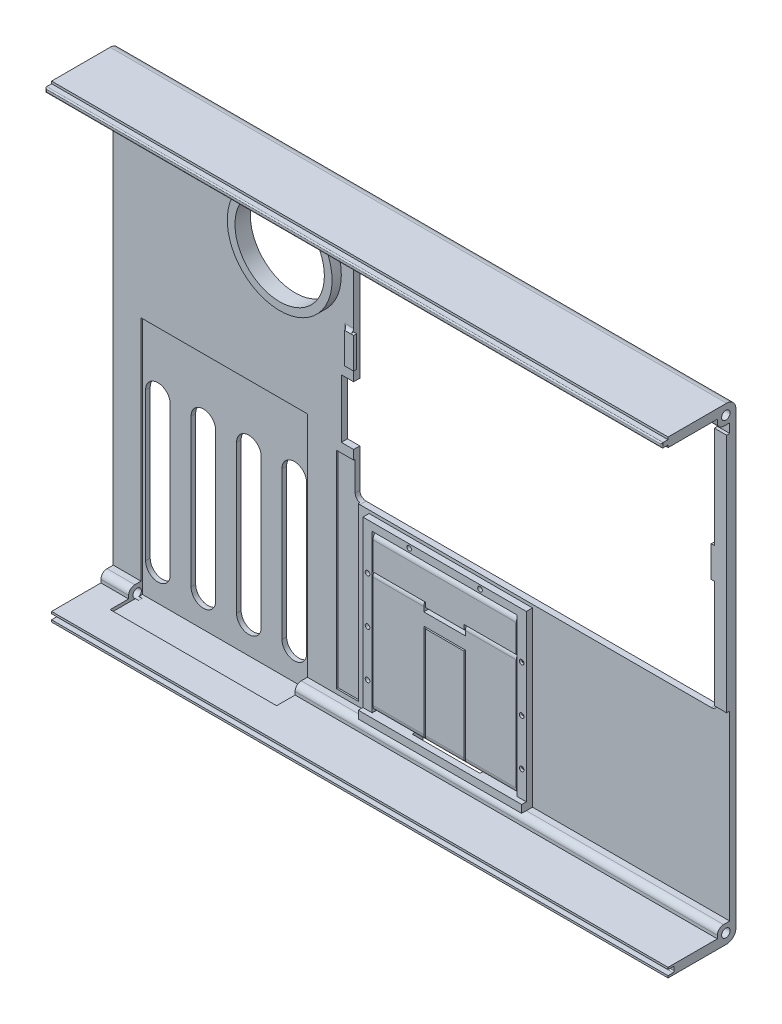
SolidWorks part; units mm, degrees
ref_plane "Front Plane" through (0, 0, 0) normal (0, 0, 1) x (1, 0, 0)
ref_plane "Top Plane" through (0, 0, 0) normal (0, 1, 0) x (1, 0, 0)
ref_plane "Right Plane" through (0, 0, 0) normal (1, 0, 0) x (0, 0, -1)
sketch "Sketch1" plane through (0, 0, 0) normal (0, 0, 1) x (1, 0, 0)
  line L1 (105, -90.3987) -> (-95, -90.3987)
  line L2 (105, -90.3987) -> (105, 61.6013)
  line L3 (105, 61.6013) -> (-95, 61.6013)
  line L4 (-95, -90.3987) -> (-95, 61.6013)
  line L5 (105, -90.3987) -> (-95, 61.6013) construction
  line L6 (105, 61.6013) -> (-95, -90.3987) construction
  point P0 (5, -14.3987)
  dimension "D1" = 200
  dimension "D2" = 152
extrude "body" add sketch "Sketch1" along normal blind 2
sketch "Sketch3" plane through (0, 0, 0) normal (0, 0, -1) x (-1, 0, 0)
  line L0 (95, -54.3987) -> (-105, -54.3987) construction
  line L1 (95, 61.6013) -> (95, -90.3987) construction
  line L2 (-105, -90.3987) -> (-105, 61.6013) construction
  line L3 (66.25, -78.3987) -> (66.25, -30.3987) construction
  line L4 (62.25, -78.3987) -> (62.25, -30.3987)
  line L5 (70.25, -78.3987) -> (70.25, -30.3987)
  line L6 (95, -30.3987) -> (-105, -30.3987) construction
  line L7 (81, -78.3987) -> (81, -30.3987) construction
  line L8 (95, -78.3987) -> (-105, -78.3987) construction
  line L9 (77, -78.3987) -> (77, -30.3987)
  line L10 (85, -78.3987) -> (85, -30.3987)
  line L11 (51.5, -78.3987) -> (51.5, -30.3987) construction
  line L12 (47.5, -78.3987) -> (47.5, -30.3987)
  line L13 (55.5, -78.3987) -> (55.5, -30.3987)
  line L14 (36.75, -78.3987) -> (36.75, -30.3987) construction
  line L15 (32.75, -78.3987) -> (32.75, -30.3987)
  line L16 (40.75, -78.3987) -> (40.75, -30.3987)
  line L17 (95, -90.3987) -> (95, 61.6013) construction
  line L18 (-105, 61.6013) -> (95, 61.6013) construction
  line L19 (95, -90.3987) -> (-105, -90.3987) construction
  line L20 (-105, -90.3987) -> (-105, 61.6013) construction
  circle A0 centre (38, 34.1013) radius 14.5
  arc A1 (62.25, -78.3987) -> (70.25, -78.3987) centre (66.25, -78.3987) ccw
  arc A2 (70.25, -30.3987) -> (62.25, -30.3987) centre (66.25, -30.3987) ccw
  arc A3 (77, -78.3987) -> (85, -78.3987) centre (81, -78.3987) ccw
  arc A4 (85, -30.3987) -> (77, -30.3987) centre (81, -30.3987) ccw
  arc A5 (47.5, -78.3987) -> (55.5, -78.3987) centre (51.5, -78.3987) ccw
  arc A6 (55.5, -30.3987) -> (47.5, -30.3987) centre (51.5, -30.3987) ccw
  arc A7 (32.75, -78.3987) -> (40.75, -78.3987) centre (36.75, -78.3987) ccw
  arc A8 (40.75, -30.3987) -> (32.75, -30.3987) centre (36.75, -30.3987) ccw
  point P10 (66.25, -54.3987)
  point P21 (81, -54.3987)
  point P27 (51.5, -54.3987)
  point P34 (36.75, -54.3987)
  dimension "D1" = 29
  dimension "D2" = 27.5
  dimension "D3" = 57
  dimension "D4" = 10
  dimension "D5" = 12
  dimension "D6" = 24
  dimension "D7" = 6.75
  dimension "D8" = 8
  dimension "D9" = 8
  dimension "D10" = 8
  dimension "D11" = 8
  dimension "D12" = 6.75
  dimension "D13" = 52.25
  dimension "D14" = 6.75
extrude "fan_exhaust_grill" cut sketch "Sketch3" against normal through all
sketch "Sketch12" plane through (0, 0, 2) normal (0, 0, 1) x (1, 0, 0)
  line L0 (-95, -90.3987) -> (-95, 61.6013) construction
  line L1 (105, -90.3987) -> (-95, -90.3987)
  line L2 (105, -90.3987) -> (105, -84.3987)
  line L3 (105, -84.3987) -> (-95, -84.3987)
  line L4 (-95, -90.3987) -> (-95, -84.3987)
  line L6 (105, 61.6013) -> (-95, 61.6013)
  line L7 (105, 61.6013) -> (105, 55.6013)
  line L8 (105, 55.6013) -> (-95, 55.6013)
  line L9 (-95, 61.6013) -> (-95, 55.6013)
  dimension "D1" = 6
  dimension "D2" = 6
extrude "side_walls" add sketch "Sketch12" along normal blind 20
sketch "Sketch14" plane through (105, 0, 0) normal (1, 0, 0) x (0, 0, -1)
  line L0 (-22, -90.3987) -> (0, -90.3987) construction
  line L1 (0, -90.3987) -> (0, 61.6013) construction
  line L2 (-22, 61.6013) -> (0, 61.6013) construction
  circle A0 centre (-3.25, -87.1487) radius 1.375
  circle A1 centre (-3.25, 58.3513) radius 1.375
  dimension "D1" = 2.75
  dimension "D2" = 2.75
  dimension "D3" = 3.25
  dimension "D4" = 3.25
  dimension "D5" = 3.25
  dimension "D6" = 3.25
  dimension "D7" = 145.5
extrude "mount_holes_l" cut sketch "Sketch14" against normal blind 10 and the other way through all
sketch "Sketch16" plane through (-95, 0, 0) normal (-1, 0, 0) x (0, 0, 1)
  line L0 (0, -90.3987) -> (0, 61.6013) construction
  line L2 (22, 61.6013) -> (0, 61.6013) construction
  line L3 (22, -90.3987) -> (0, -90.3987) construction
  circle A0 centre (3.25, -87.1487) radius 1.375
  circle A1 centre (3.25, 58.3513) radius 1.375
  dimension "D1" = 2.75
  dimension "D4" = 2.75
  dimension "D2" = 3.25
  dimension "D3" = 3.25
  dimension "D5" = 3.25
  dimension "D6" = 3.25
extrude "mount_holes_r" cut sketch "Sketch16" against normal blind 10
sketch "Sketch18" plane through (105, 0, 0) normal (1, 0, 0) x (0, 0, -1)
  line L1 (-22, -84.3987) -> (-6, -84.3987)
  line L2 (-22, -84.3987) -> (-22, -87.3987)
  line L3 (-22, -87.3987) -> (-6, -87.3987)
  line L4 (-6, -84.3987) -> (-6, -87.3987)
  line L5 (-22, 55.6013) -> (-6, 55.6013)
  line L6 (-22, 55.6013) -> (-22, 58.6013)
  line L7 (-22, 58.6013) -> (-6, 58.6013)
  line L8 (-6, 55.6013) -> (-6, 58.6013)
  dimension "D1" = 3
  dimension "D2" = 16
  dimension "D3" = 3
  dimension "D4" = 16
extrude "wall_reduce" cut sketch "Sketch18" against normal through all
sketch "Sketch19" plane through (0, 0, 22) normal (0, 0, 1) x (1, 0, 0)
  line L0 (-95, -90.3987) -> (-95, 61.6013) construction
  line L1 (-95, -89.7487) -> (105, -89.7487)
  line L2 (-95, -89.7487) -> (-95, -88.0487)
  line L3 (-95, -88.0487) -> (105, -88.0487)
  line L4 (105, -89.7487) -> (105, -88.0487)
  line L5 (105, -90.3987) -> (105, 61.6013) construction
  line L6 (-95, -90.3987) -> (105, -90.3987) construction
  line L7 (-95, -87.3987) -> (105, -87.3987) construction
  dimension "D1" = 0.65
  dimension "D2" = 1.7
  dimension "D3" = 0.65
extrude "groove" cut sketch "Sketch19" against normal blind 2
sketch "Sketch20" plane through (0, 0, 22) normal (0, 0, 1) x (1, 0, 0)
  line L0 (-95, -90.3987) -> (-95, 61.6013) construction
  line L1 (-95, 59.3513) -> (105, 59.3513)
  line L2 (-95, 59.3513) -> (-95, 60.8513)
  line L3 (-95, 60.8513) -> (105, 60.8513)
  line L4 (105, 59.3513) -> (105, 60.8513)
  line L5 (105, -90.3987) -> (105, 61.6013) construction
  line L6 (105, 61.6013) -> (-95, 61.6013) construction
  dimension "D1" = 0.75
  dimension "D2" = 1.5
extrude "notch" add sketch "Sketch20" along normal blind 2
sketch "Sketch21" plane through (0, 0, 2) normal (0, 0, 1) x (1, 0, 0)
  line L0 (105, -90.3987) -> (105, 61.6013) construction
  line L1 (101, -27.3987) -> (-17, -27.3987)
  line L2 (101, -27.3987) -> (101, 55.1013)
  line L3 (101, 55.1013) -> (-17, 55.1013)
  line L4 (-17, -27.3987) -> (-17, 55.1013)
  line L5 (105, 61.6013) -> (-95, 61.6013) construction
  dimension "D1" = 118
  dimension "D2" = 82.5
  dimension "D3" = 4
  dimension "D4" = 6.5
extrude "batt_cut" cut sketch "Sketch21" against normal through all
fillet "Fillet1" radius 3 2 edges at (5, -90.3987, 0) (5, 61.6013, 0)
fillet "Fillet2" radius 2 2 edges at (5, -84.3987, 6) (5, 55.6013, 6)
fillet "Fillet3" radius 0.4 6 edges at (5, 60.8513, 24) (105, 60.1013, 24) (5, 59.3513, 24) (-95, 60.1013, 24) (5, -89.7487, 20) (5, -88.0487, 20)
fillet "Fillet4" radius 2 4 edges at (-17, -27.3987, 1) (101, -27.3987, 1) (101, 55.1013, 1) (-17, 55.1013, 1)
sketch "Sketch22" plane through (0, 0, 2) normal (0, 0, 1) x (1, 0, 0)
  circle A0 centre (-38, 34.1013) radius 14.5
  circle A1 centre (-38, 34.1013) radius 17
  dimension "D1" = 29
  dimension "D2" = 34
extrude "fan_hole_supp" add sketch "Sketch22" along normal blind 3
sketch "Sketch23" plane through (0, 0, 2) normal (0, 0, 1) x (1, 0, 0)
  line L0 (105, -90.3987) -> (105, 61.6013) construction
  line L1 (105, 52.6013) -> (101, 52.6013)
  line L2 (105, 52.6013) -> (105, -25.3987)
  line L3 (105, -25.3987) -> (101, -25.3987)
  line L4 (101, 52.6013) -> (101, -25.3987)
  arc A0 (99, -27.3987) -> (101, -25.3987) centre (99, -25.3987) ccw construction
  dimension "D1" = 78
  dimension "D2" = 4
extrude "batt_cut_supp" add sketch "Sketch23" along normal blind 1
sketch "Sketch24" plane through (0, 0, 2) normal (0, 0, 1) x (1, 0, 0)
  line L0 (-95, -90.3987) -> (-95, 61.6013) construction
  line L1 (-86, -10.3987) -> (-32, -10.3987)
  line L2 (-86, -10.3987) -> (-86, -88.3987)
  line L3 (-86, -88.3987) -> (-32, -88.3987)
  line L4 (-32, -10.3987) -> (-32, -88.3987)
  line L5 (-95, -90.3987) -> (105, -90.3987) construction
  line L7 (-22.5, -15.8987) -> (-15.5, -15.8987)
  line L8 (-22.5, -15.8987) -> (-22.5, -82.8987)
  line L9 (-22.5, -82.8987) -> (-15.5, -82.8987)
  line L10 (-15.5, -15.8987) -> (-15.5, -82.8987)
  dimension "D1" = 9
  dimension "D2" = 2
  dimension "D3" = 54
  dimension "D4" = 78
  dimension "D5" = 9.5
  dimension "D6" = 7
  dimension "D7" = 67
  dimension "D8" = 5.5
  dimension "D9" = 5.5
extrude "Cut-Extrude1" cut sketch "Sketch24" against normal blind 10.5 from offset 10
sketch "Sketch25" plane through (0, 0, 2) normal (0, 0, 1) x (1, 0, 0)
  line L7 (-17, 53.1013) -> (-17, -15.8987) construction
  line L8 (-17, 6.1013) -> (-21, 6.1013)
  line L9 (-17, 6.1013) -> (-17, -12.8987)
  line L10 (-17, -12.8987) -> (-21, -12.8987)
  line L11 (-21, 6.1013) -> (-21, -12.8987)
  line L12 (-15, -27.3987) -> (99, -27.3987) construction
  dimension "D1" = 14.5
  dimension "D2" = 19
  dimension "D3" = 4
extrude "Cut-Extrude2" cut sketch "Sketch25" against normal through all
sketch "Sketch26" plane through (0, 0, 2) normal (0, 0, 1) x (1, 0, 0)
  line L0 (-17, 53.1013) -> (-17, 6.1013) construction
  line L1 (-17, 20.1013) -> (-19, 20.1013)
  line L2 (-17, 20.1013) -> (-17, 10.1013)
  line L3 (-17, 10.1013) -> (-19, 10.1013)
  line L4 (-19, 20.1013) -> (-19, 10.1013)
  line L10 (99, 55.1013) -> (-15, 55.1013) construction
  dimension "D4" = 2
  dimension "D5" = 10
  dimension "D6" = 35
extrude "Boss-Extrude1" add sketch "Sketch26" along normal blind 1
sketch "Sketch27" plane through (-17, 0, 0) normal (1, 0, 0) x (0, 0, -1)
  line L0 (-3, 10.1013) -> (-3, 20.1013) construction
  line L1 (-3, 20.1013) -> (-2, 20.1013)
  line L2 (-3, 20.1013) -> (-3, 10.1013)
  line L3 (-3, 10.1013) -> (-2, 10.1013)
  line L4 (-2, 20.1013) -> (-2, 10.1013)
  line L5 (-3, 20.1013) -> (-2, 20.1013) construction
extrude "Boss-Extrude2" add sketch "Sketch27" along normal blind 1
sketch "Sketch28" plane through (101, 0, 0) normal (-1, 0, 0) x (0, 0, 1)
  line L0 (0, -25.3987) -> (0, 53.1013) construction
  line L1 (2, 9.6013) -> (3, 9.6013)
  line L2 (2, 9.6013) -> (2, 19.6013)
  line L3 (2, 19.6013) -> (3, 19.6013)
  line L4 (3, 9.6013) -> (3, 19.6013)
  line L5 (3, 52.6013) -> (2, 52.6013) construction
  dimension "D1" = 1
  dimension "D2" = 2
  dimension "D3" = 10
  dimension "D4" = 33
extrude "Boss-Extrude3" add sketch "Sketch28" along normal blind 1
fillet "Fillet5" radius 1 3 edges at (-18, 20.1013, 2) (-18, 10.1013, 2) (-19, 15.1013, 2)
sketch "Sketch29" plane through (0, 0, 2) normal (0, 0, 1) x (1, 0, 0)
  line L1 (-9, -30.8987) -> (38, -30.8987)
  line L2 (-9, -30.8987) -> (-9, -81.8987)
  line L3 (-9, -81.8987) -> (38, -81.8987)
  line L4 (38, -30.8987) -> (38, -81.8987)
  line L5 (105, -90.3987) -> (105, 61.6013) construction
  line L7 (-95, -90.3987) -> (105, -90.3987) construction
  dimension "D1" = 67
  dimension "D2" = 47
  dimension "D3" = 51
  dimension "D4" = 8.5
extrude "stand_cut" cut sketch "Sketch29" against normal through all
sketch "Sketch30" plane through (0, 0, 2) normal (0, 0, 1) x (1, 0, 0)
  line L0 (-9, -81.8987) -> (38, -30.8987) construction
  line L1 (38, -30.8987) -> (-9, -30.8987) construction
  line L2 (38, -81.8987) -> (38, -30.8987) construction
  line L3 (-9, -30.8987) -> (38, -81.8987) construction
  line L5 (41, -84.3987) -> (-12, -84.3987)
  line L6 (41, -84.3987) -> (41, -28.3987)
  line L7 (41, -28.3987) -> (-12, -28.3987)
  line L8 (-12, -84.3987) -> (-12, -28.3987)
  line L9 (41, -84.3987) -> (-12, -28.3987) construction
  line L10 (41, -28.3987) -> (-12, -84.3987) construction
  line L11 (38, -81.8987) -> (-9, -81.8987)
  line L12 (38, -81.8987) -> (38, -30.8987)
  line L13 (38, -30.8987) -> (-9, -30.8987)
  line L14 (-9, -81.8987) -> (-9, -30.8987)
  line L15 (38, -81.8987) -> (-9, -30.8987) construction
  line L16 (38, -30.8987) -> (-9, -81.8987) construction
  point P11 (14.5, -56.3987)
  point P16 (14.5, -56.3987)
  dimension "D1" = 3
  dimension "D2" = 2.5
extrude "stand_extra_support" add sketch "Sketch30" along normal blind 2
sketch "Sketch31" plane through (-9, 0, 0) normal (1, 0, 0) x (0, 0, -1)
  line L0 (-2, -24.3792) -> (-2, -81.8987) construction
  line L1 (0, -81.8987) -> (-4, -81.8987) construction
  line L2 (0, -30.8987) -> (0, -81.8987) construction
  line L3 (-0.75, -80.8987) -> (-3.25, -80.8987)
  line L4 (-0.75, -80.8987) -> (-0.75, -37.8987)
  line L5 (-0.75, -37.8987) -> (-3.25, -37.8987)
  line L6 (-3.25, -80.8987) -> (-3.25, -37.8987)
  line L7 (-0.75, -80.8987) -> (-3.25, -37.8987) construction
  line L8 (-0.75, -37.8987) -> (-3.25, -80.8987) construction
  line L9 (0, -30.8987) -> (-4, -30.8987) construction
  circle A0 centre (-2, -33.1487) radius 1.125
  point P4 (-2, -59.3987)
  dimension "D6" = 2.25
  dimension "D1" = 1
  dimension "D2" = 43
  dimension "D3" = 2.5
  dimension "D4" = 0.75
  dimension "D5" = 2.25
extrude "stand_right_groove" cut sketch "Sketch31" against normal blind 2
sketch "Sketch32" plane through (38, 0, 0) normal (-1, 0, 0) x (0, 0, 1)
  line L0 (2, -81.8987) -> (2, -30.8421) construction
  line L1 (0, -81.8987) -> (4, -81.8987) construction
  line L2 (0, -30.8987) -> (4, -30.8987) construction
  line L3 (3.25, -37.8987) -> (0.75, -37.8987)
  line L4 (3.25, -37.8987) -> (3.25, -80.8987)
  line L5 (3.25, -80.8987) -> (0.75, -80.8987)
  line L6 (0.75, -37.8987) -> (0.75, -80.8987)
  line L7 (3.25, -37.8987) -> (0.75, -80.8987) construction
  line L8 (3.25, -80.8987) -> (0.75, -37.8987) construction
  circle A0 centre (2, -33.1487) radius 1.125
  point P4 (2, -59.3987)
  dimension "D5" = 2.25
  dimension "D1" = 2.5
  dimension "D2" = 43
  dimension "D3" = 1
  dimension "D4" = 2.25
extrude "stand_left_groove" cut sketch "Sketch32" against normal blind 2
fillet "Fillet6" radius 1 8 edges at (40, -37.8987, 2) (40, -59.3987, 3.25) (40, -80.8987, 2) (40, -59.3987, 0.75) (-11, -37.8987, 2) (-11, -59.3987, 0.75) (-11, -80.8987, 2) (-11, -59.3987, 3.25)
sketch "Sketch33" plane through (0, 0, 0) normal (0, 0, -1) x (-1, 0, 0)
  line L0 (-14.5, -81.8987) -> (-14.5, -30.8987) construction
  line L1 (9, -81.8987) -> (-38, -81.8987) construction
  line L2 (-38, -30.8987) -> (9, -30.8987) construction
  line L3 (-105, -87.3987) -> (95, -87.3987) construction
  line L4 (-3.5, -86.3987) -> (-25.5, -86.3987)
  line L5 (-3.5, -86.3987) -> (-3.5, -81.8987)
  line L6 (-3.5, -81.8987) -> (-25.5, -81.8987)
  line L7 (-25.5, -86.3987) -> (-25.5, -81.8987)
  line L8 (-3.5, -86.3987) -> (-25.5, -81.8987) construction
  line L9 (-3.5, -81.8987) -> (-25.5, -86.3987) construction
  point P6 (-14.5, -84.1487)
  dimension "D1" = 1
  dimension "D2" = 4.5
  dimension "D3" = 22
extrude "finger_notch" cut sketch "Sketch33" against normal blind 3.5
sketch "Sketch34" plane through (0, 0, 4) normal (0, 0, 1) x (1, 0, 0)
  line L0 (41, -84.3987) -> (41, -28.3987) construction
  line L1 (-12, -84.3987) -> (41, -84.3987)
  line L2 (-12, -84.3987) -> (-12, -81.8987)
  line L3 (-12, -81.8987) -> (41, -81.8987)
  line L4 (41, -84.3987) -> (41, -81.8987)
  dimension "D1" = 2.5
extrude "back_lid_ext" add sketch "Sketch34" along normal blind 1.5
sketch "Sketch36" plane through (0, 0, 0) normal (0, 0, -1) x (-1, 0, 0)
  line L0 (-38, -30.8987) -> (9, -30.8987) construction
  line L1 (-37.75, -31.1487) -> (8.75, -31.1487)
  line L2 (-37.75, -31.1487) -> (-37.75, -81.6487)
  line L3 (-37.75, -81.6487) -> (8.75, -81.6487)
  line L4 (8.75, -31.1487) -> (8.75, -81.6487)
  line L5 (-38, -81.8987) -> (-38, -30.8987) construction
  dimension "D1" = 50.5
  dimension "D2" = 0.25
  dimension "D3" = 0.25
  dimension "D4" = 46.5
extrude "st_body" add sketch "Sketch36" against normal blind 4 separate body
sketch "Sketch37" plane through (0, 0, 0) normal (0, 0, -1) x (-1, 0, 0)
  line L0 (-37.75, -41.1487) -> (-20.75, -41.1487)
  line L1 (-37.75, -31.1487) -> (-37.75, -81.6487) construction
  line L2 (-20.75, -41.1487) -> (-20.75, -81.6487)
  line L3 (-37.75, -81.6487) -> (8.75, -81.6487) construction
  line L4 (-37.75, -41.6487) -> (-21.25, -41.6487)
  line L5 (-21.25, -41.6487) -> (-21.25, -81.6487)
  line L6 (8.75, -41.1487) -> (-8.25, -41.1487)
  line L7 (8.75, -81.6487) -> (8.75, -31.1487) construction
  line L8 (-8.25, -41.1487) -> (-8.25, -81.6487)
  line L9 (8.75, -41.6487) -> (-7.75, -41.6487)
  line L10 (-7.75, -41.6487) -> (-7.75, -81.6487)
  line L11 (-37.75, -41.1487) -> (-37.75, -41.6487)
  line L12 (8.75, -41.1487) -> (8.75, -41.6487)
  line L13 (-21.25, -81.6487) -> (-20.75, -81.6487)
  line L14 (-8.25, -81.6487) -> (-7.75, -81.6487)
  line L15 (8.75, -31.1487) -> (-37.75, -31.1487) construction
  dimension "D1" = 0.5
  dimension "D2" = 0.5
  dimension "D3" = 0.5
  dimension "D4" = 0.5
  dimension "D5" = 10
  dimension "D6" = 10
  dimension "D7" = 16.5
  dimension "D8" = 16.5
extrude "st_body_cut" cut sketch "Sketch37" against normal blind 4
fillet "Fillet8" radius 2 4 edges at (29.5, -41.6487, 4) (29.5, -41.6487, 0) (29.5, -81.6487, 4) (29.5, -81.6487, 0)
fillet "Fillet9" radius 2 4 edges at (-0.5, -41.6487, 4) (-0.5, -81.6487, 4) (-0.5, -81.6487, 0) (-0.5, -41.6487, 0)
fillet "Fillet10" radius 2 4 edges at (14.5, -31.1487, 0) (14.5, -81.6487, 0) (14.5, -81.6487, 4) (14.5, -31.1487, 4)
sketch "Sketch39" plane through (-8.75, 0, 0) normal (-1, 0, 0) x (0, 0, 1)
  line L0 (2, -41.6487) -> (2, -81.6487) construction
  circle A0 centre (2, -79.6487) radius 1.25
  dimension "D2" = 2.5
  dimension "D1" = 2
extrude "st_hinge_hole_l" cut sketch "Sketch39" against normal blind 10 from offset 6.5 offset against normal yes
sketch "Sketch40" plane through (37.75, 0, 0) normal (1, 0, 0) x (0, 0, -1)
  line L0 (-2, -41.6487) -> (-2, -81.6487) construction
  circle A0 centre (-2, -79.6487) radius 1.25
  dimension "D2" = 2.5
  dimension "D1" = 2
extrude "st_hinge_hole_r" cut sketch "Sketch40" against normal blind 10 from offset 6.5 offset against normal yes
sketch "Sketch41" plane through (20.75, 0, 0) normal (1, 0, 0) x (0, 0, -1)
  line L0 (-2, -41.1487) -> (-2, -81.6487) construction
  line L1 (-4, -41.1487) -> (0, -41.1487) construction
  circle A0 centre (-2, -79.6487) radius 0.9
  dimension "D2" = 1.8
  dimension "D1" = 2
extrude "st_hinge_rod" add sketch "Sketch41" against normal blind 26.5 from offset 7
sketch "Sketch42" plane through (0, 0, 4) normal (0, 0, -1) x (-1, 0, 0)
  line L0 (-21.25, -43.6487) -> (-7.75, -43.6487) construction
  line L1 (-21.25, -43.6487) -> (-37.75, -43.6487) construction
  line L2 (-21.25, -43.6487) -> (-21.25, -79.6487) construction
  line L3 (-20.75, -79.6487) -> (-20.75, -41.1487) construction
  line L4 (-20.75, -43.6487) -> (-8.25, -43.6487)
  line L5 (-20.75, -43.6487) -> (-20.75, -49.6487)
  line L6 (-20.75, -49.6487) -> (-8.25, -49.6487)
  line L7 (-8.25, -43.6487) -> (-8.25, -49.6487)
  line L8 (-8.25, -41.1487) -> (-8.25, -79.6487) construction
  dimension "D1" = 6
sketch "Sketch43" plane through (7.75, 0, 0) normal (-1, 0, 0) x (0, 0, 1)
  line L5 (4, -43.6487) -> (4, -79.6487) construction
  line L6 (4, -45.1487) -> (2.5, -45.1487)
  line L7 (4, -45.1487) -> (4, -49.1487)
  line L8 (4, -49.1487) -> (2.5, -49.1487)
  line L9 (2.5, -45.1487) -> (2.5, -49.1487)
  dimension "D4" = 1.5
  dimension "D5" = 3.5
  dimension "D6" = 4
sketch "Sketch44" plane through (-8.75, 0, 0) normal (-1, 0, 0) x (0, 0, 1)
  line L0 (2, -31.1487) -> (2, -81.6487) construction
  arc A0 (2, -81.6487) -> (4, -79.6487) centre (2, -79.6487) ccw construction
  circle A1 centre (2, -33.1487) radius 1
  circle A2 centre (2, -43.6487) radius 1
  dimension "D2" = 2
  dimension "D4" = 2
  dimension "D1" = 2
  dimension "D3" = 2
extrude "st_bumps_l" add sketch "Sketch44" along normal blind 1.5
sketch "Sketch45" plane through (37.75, 0, 0) normal (1, 0, 0) x (0, 0, -1)
  line L0 (-2, -31.1487) -> (-2, -81.6487) construction
  circle A1 centre (-2, -43.6487) radius 1
  circle A2 centre (-2, -33.1487) radius 1
  dimension "D2" = 2
  dimension "D4" = 2
  dimension "D1" = 2
  dimension "D3" = 2
extrude "st_bumps_r" add sketch "Sketch45" along normal blind 1.5
sketch "Sketch46" plane through (-8.75, 0, 0) normal (-1, 0, 0) x (0, 0, 1)
  line L0 (2, -41.6487) -> (2, -81.6487) construction
  arc A0 (2, -41.6487) -> (0, -43.6487) centre (2, -43.6487) ccw construction
  arc A1 (2, -81.6487) -> (4, -79.6487) centre (2, -79.6487) ccw construction
  circle A2 centre (2, -79.6487) radius 1
  dimension "D2" = 2
  dimension "D1" = 2
extrude "st_mini_bump_l" add sketch "Sketch46" along normal blind 0.75
sketch "Sketch47" plane through (37.75, 0, 0) normal (1, 0, 0) x (0, 0, -1)
  line L0 (-2, -41.6487) -> (-2, -81.6487) construction
  circle A0 centre (-2, -79.6487) radius 1
  dimension "D2" = 2
  dimension "D1" = 2
extrude "st_mini_bump_r" add sketch "Sketch47" along normal blind 0.75
sketch "Sketch48" plane through (37.75, 0, 0) normal (1, 0, 0) x (0, 0, -1)
  line L0 (-2, -41.6487) -> (-2, -43.6487) construction
  line L1 (-4, -43.6487) -> (0, -43.6487) construction
  line L2 (0, -43.6487) -> (0, -79.6487) construction
  line L3 (-4, -79.6487) -> (-4, -41.1487) construction
  line L4 (0, -79.6487) -> (0, -41.1487) construction
  line L5 (0, -42.1487) -> (0, -40.6487)
  line L6 (0, -33.1487) -> (0, -41.1487) construction
  line L7 (0, -40.6487) -> (-4, -40.6487)
  line L8 (-4, -40.6487) -> (-4, -42.1487)
  line L9 (-4, -41.1487) -> (0, -41.1487) construction
  arc A0 (-4, -42.1487) -> (0, -42.1487) centre (-2, -43.6487) cw
  dimension "D1" = 2.5
  dimension "D2" = 0.5
extrude "st_hook_material_r" add sketch "Sketch48" against normal blind 17
pattern_linear "LPattern1" count 2 spacing 29.5 along (-1, 0, 0) of "st_hook_material_r"
extrude "st_hook_cut" cut sketch "Sketch42" along normal blind 2
extrude "st_hook" add sketch "Sketch43" against normal blind 13.5
fillet "Fillet11" radius 4 1 edges at (14.5, -86.3987, 3.5)
sketch "Sketch49" plane through (0, 0, 4) normal (0, 0, 1) x (1, 0, 0)
  line L0 (-12, -29.6487) -> (41, -29.6487) construction
  line L1 (-12, -28.3987) -> (-12, -81.8987) construction
  line L2 (39.5, -28.3987) -> (39.5, -81.8987) construction
  line L3 (41, -28.3987) -> (-12, -28.3987) construction
  line L4 (41, -81.8987) -> (-12, -81.8987) construction
  line L5 (-10.5, -28.3987) -> (-10.5, -81.8987) construction
  line L6 (41, -81.8987) -> (41, -28.3987) construction
  circle A0 centre (3, -29.6487) radius 0.75
  circle A1 centre (26, -29.6487) radius 0.75
  circle A2 centre (-10.5, -43.3987) radius 0.75
  circle A3 centre (-10.5, -58.3987) radius 0.75
  circle A4 centre (-10.5, -73.3987) radius 0.75
  circle A5 centre (39.5, -58.3987) radius 0.75
  circle A6 centre (39.5, -73.3987) radius 0.75
  circle A7 centre (39.5, -43.3987) radius 0.75
  dimension "D4" = 1.5
  dimension "D5" = 1.5
  dimension "D6" = 1.5
  dimension "D7" = 1.5
  dimension "D8" = 1.5
  dimension "D9" = 1.5
  dimension "D10" = 1.5
  dimension "D14" = 1.5
  dimension "D1" = 1.25
  dimension "D2" = 1.5
  dimension "D3" = 1.5
  dimension "D11" = 15
  dimension "D12" = 15
  dimension "D13" = 15
  dimension "D15" = 15
  dimension "D16" = 15
  dimension "D17" = 15
  dimension "D18" = 15
  dimension "D19" = 15
extrude "back_lid_holes" cut sketch "Sketch49" against normal blind 1
